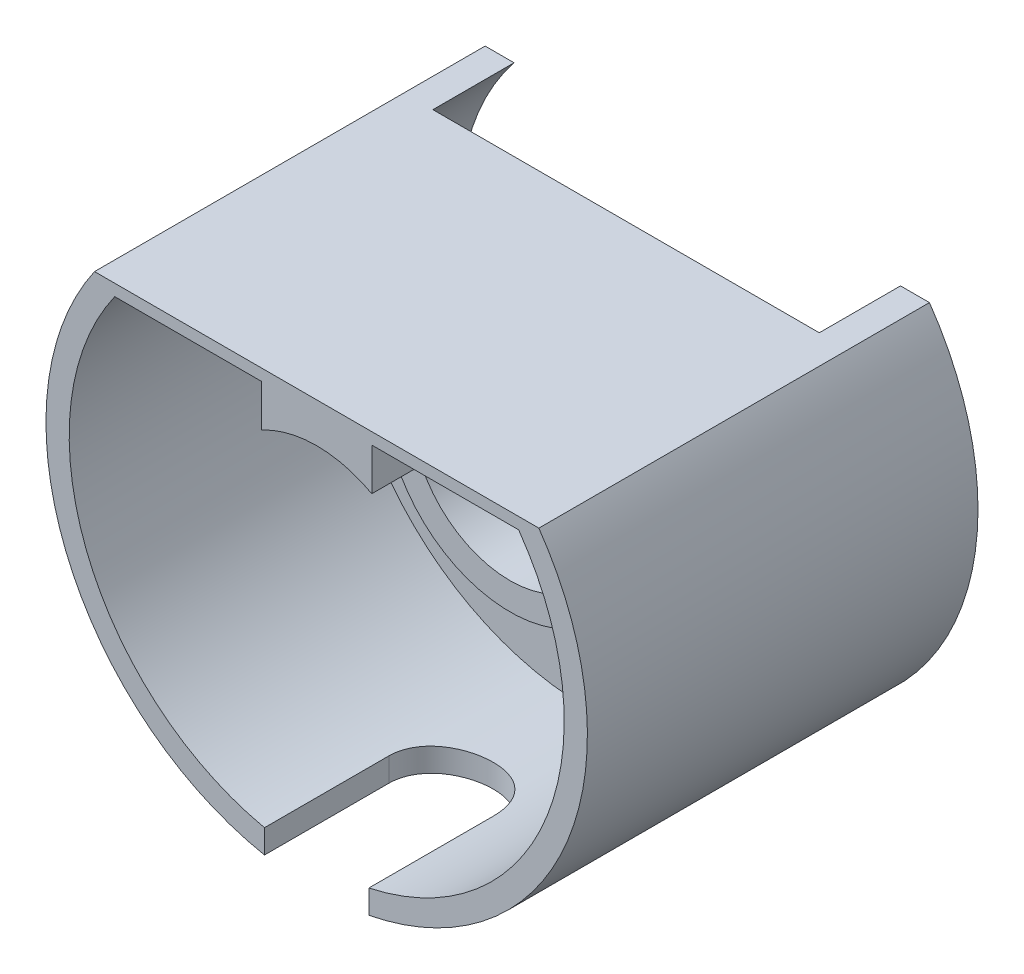
SolidWorks part; units mm, degrees
ref_plane "Front Plane" through (0, 0, 0) normal (0, 0, 1) x (1, 0, 0)
ref_plane "Top Plane" through (0, 0, 0) normal (0, 1, 0) x (1, 0, 0)
ref_plane "Right Plane" through (0, 0, 0) normal (1, 0, 0) x (0, 0, -1)
sketch "Sketch1" plane through (0, 0, 0) normal (0, 0, 1) x (1, 0, 0)
  line L0 (54.25, -85) -> (54.25, -95)
  line L5 (0, 0) -> (80, 0)
  line L6 (0, 0) -> (0, -85)
  line L7 (0, -85) -> (80, -85)
  line L8 (80, 0) -> (80, -85)
  line L10 (25.75, -85) -> (25.75, -95)
  line L11 (25.75, 0) -> (25.75, -15.8532)
  line L12 (54.25, 0) -> (54.25, -7.7906)
  line L13 (54.25, -7.7906) -> (54.25, -15.8532)
  line L14 (0, -37) -> (80, -37) construction
  line L15 (80, -30) -> (64.5204, -30)
  line L16 (80, -44) -> (64.5204, -44)
  line L17 (0, -30) -> (15.4796, -30)
  line L18 (0, -44) -> (15.4796, -44)
  line L19 (68.9, -30) -> (68.9, -44)
  line L20 (11.1, -30) -> (11.1, -44)
  line L21 (25.75, -95) -> (54.25, -95)
  line L22 (0, 0) -> (-12.2207, 0)
  line L23 (-17.4456, 3) -> (97.4456, 3)
  line L24 (80, 0) -> (92.2207, 0)
  circle A0 centre (40, -37) radius 32.5
  circle A3 centre (6, -6) radius 2
  circle A4 centre (6, -6) radius 4
  circle A5 centre (74, -79) radius 2
  circle A6 centre (74, -79) radius 4
  circle A7 centre (40, -37) radius 25.5
  circle A8 centre (40, -20.8872) radius 4
  circle A9 centre (40, -37) radius 29.7357
  circle A10 centre (40, -37) radius 64
  circle A11 centre (40, -37) radius 70
  point P12 (40, -85)
  dimension "D7" = 37
  dimension "D8" = 40
  dimension "D9" = 65
  dimension "D10" = 14.25
  dimension "D12" = 6
  dimension "D14" = 6
  dimension "D16" = 51
  dimension "D17" = 7
  dimension "D21" = 6
  dimension "D22" = 128
  dimension "D3" = 80
  dimension "D4" = 40
  dimension "D5" = 85
  dimension "D11" = 14.25
  dimension "D13" = 6
  dimension "D15" = 6
  dimension "D18" = 7
  dimension "D19" = 11.1
  dimension "D20" = 11.1
extrude "Boss-Extrude1" add sketch "Sketch1" against normal blind 21 contours L23 A11 A10 region at (92.5343, 2.5881, 0)
extrude "Boss-Extrude2" add sketch "Sketch1<29>" along normal blind 10 separate body contours L22 A10 L24 L8 L7 L0 L21 L10 L6 | L10 L21 L0 L7 | A0 L18 L6 L7 L8 L16 A6 | A7 L14 L19 L15 | A9 L14 A0 L15 | A0 L14 L8 L15 | L14 A0 L16 L8 | L14 A9 L16 A0 | L14 A7 L16 L19 | A9 L18 A0 L16 | L18 A9 L16 A7 | L14 A7 | L14 L20 L18 A7 | L14 A0 L18 A9 | L14 L6 L18 A0 | L6 L14 A0 L17 | A0 L11 L5 L6 L17 A4 | A0 L12 L5 L11 | A0 L15 L8 L5 L12 | A9 L15 A0 L13 | A9 L13 A0 L11 | A9 L11 A0 L17 | A0 L14 A9 L17 | L20 L14 A7 L17 | A7 L14 A8 | L11 A9 L17 A7 | A8 | L13 A9 L11 A7 | L15 A9 L13 A7 | L19 L14 A9 | L14 L19 A9 | A9 L14 L20 | L14 A9 L20 | A4 A3 | A3 | L24 A10 L23 L22 L5 | A6 A5 | A5 region at (67.125, -86.6305, 0) region at (40, -90, 0) region at (39.1548, -70.0248, 0) region at (76.1201, -40.5573, 0) region at (3.8799, -40.5573, 0) region at (76.1201, -33.4427, 0) region at (40, -68.8159, 0) region at (70.851, -40.5151, 0) region at (3.8799, -33.4427, 0) region at (9.149, -40.5151, 0) region at (70.1436, -11.7766, 0) region at (70.851, -33.4849, 0) region at (40, -66.1146, 0) region at (67.0266, -40.6528, 0) region at (69.2347, -39.63, 0) region at (10.2719, -12.3991, 0) region at (9.149, -33.4849, 0) region at (12.9734, -40.6528, 0) region at (10.7653, -39.63, 0) region at (40, 1.4889, 0) region at (63.8237, -18.4662, 0) region at (69.2347, -34.37, 0) region at (40, -47.8225, 0) region at (67.0266, -33.3472, 0) region at (16.1763, -18.4662, 0) region at (10.7653, -34.37, 0) region at (12.9734, -33.3472, 0) region at (40, -2.8718, 0) region at (61.6395, -20.7858, 0) region at (40, -7.0453, 0) region at (40, -26.4513, 0) region at (18.3605, -20.7858, 0) region at (40, -10.7258, 0) region at (6, -6, 0) region at (2.1131, -6, 0) region at (74, -79, 0) region at (70.1131, -79, 0) region at (40, -20.8872, 0)
sketch "Sketch1<29>" plane through (0, 0, 0) normal (0, 0, 1) x (1, 0, 0) same geometry as "Sketch1"
extrude "Boss-Extrude3" add sketch "Sketch1<30>" along normal blind 30 contours A8 | A0 | A7 region at (40, -20.8872, 0)
sketch "Sketch1<30>" plane through (0, 0, 0) normal (0, 0, 1) x (1, 0, 0) same geometry as "Sketch1"
extrude "Boss-Extrude5" add sketch "Sketch1<33>" along normal blind 40 contours A0 L14 A9 L17 | L6 L14 A0 L17 | L14 A0 L18 A9 | L14 L6 L18 A0 | A9 L14 A0 L15 | A0 L14 L8 L15 | L14 A0 L16 L8 | L14 A9 L16 A0 region at (76.1201, -40.5573, 0) region at (3.8799, -40.5573, 0) region at (76.1201, -33.4427, 0) region at (70.851, -40.5151, 0) region at (3.8799, -33.4427, 0) region at (9.149, -40.5151, 0) region at (70.851, -33.4849, 0) region at (9.149, -33.4849, 0)
sketch "Sketch1<33>" plane through (0, 0, 0) normal (0, 0, 1) x (1, 0, 0) same geometry as "Sketch1"
extrude "Boss-Extrude6" add sketch "Sketch1<34>" along normal blind 80 contours A0 L12 L5 L11 | A9 L13 A0 L11 region at (40, -2.8718, 0) region at (40, -7.0453, 0)
sketch "Sketch1<34>" plane through (0, 0, 0) normal (0, 0, 1) x (1, 0, 0) same geometry as "Sketch1"
extrude "Boss-Extrude7" add sketch "Sketch1<35>" along normal blind 80 contours L23 A11 A10 | L24 A10 L23 L22 L5 region at (40, 1.4889, 0) region at (92.5343, 2.5881, 0)
sketch "Sketch1<35>" plane through (0, 0, 0) normal (0, 0, 1) x (1, 0, 0) same geometry as "Sketch1"
ref_plane "Plane1" through (0, 0, 10) normal (0, 0, 1) x (1, 0, 0)
sketch "Sketch2" plane through (0, 0, 10) normal (0, 0, 1) x (1, 0, 0)
  circle A1 centre (40, -37) radius 64
  circle A2 centre (40, -37) radius 70
ref_plane "Plane2" through (0, -60, 0) normal (0, -1, 0) x (-1, 0, 0)
sketch "Sketch4" plane through (0, -60, 0) normal (0, -1, 0) x (-1, 0, 0)
  line L0 (-40, -80) -> (-40, -47.8336) construction
  line L1 (-110, -80) -> (30, -80) construction
  line L2 (-53.5, -80) -> (-53.5, -47.8336)
  line L3 (-26.5, -80) -> (-26.5, -47.8336)
  arc A0 (-53.5, -80) -> (-26.5, -80) centre (-40, -80) ccw
  arc A1 (-26.5, -47.8336) -> (-53.5, -47.8336) centre (-40, -47.8336) ccw
  point P4 (-40, -63.9168)
  point P9 (-40, -44.9377)
  point P10 (0, 0)
  point P11 (-40, -47.8336)
extrude "Cut-Extrude2" cut sketch "Sketch4" along normal blind 99
